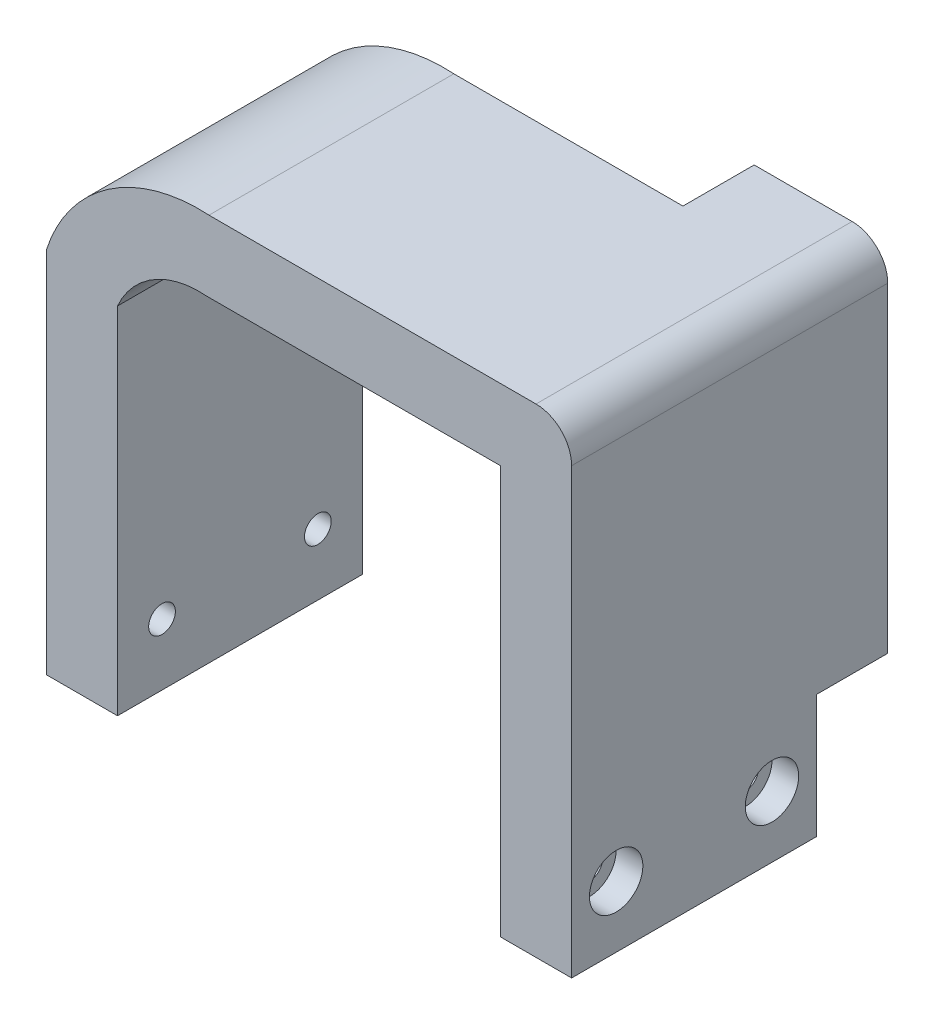
SolidWorks part; units mm, degrees
ref_plane "Front Plane" through (0, 0, 0) normal (0, 0, 1) x (1, 0, 0)
ref_plane "Top Plane" through (0, 0, 0) normal (0, 1, 0) x (1, 0, 0)
ref_plane "Right Plane" through (0, 0, 0) normal (1, 0, 0) x (0, 0, -1)
sketch "Sketch1" plane through (0, 0, 0) normal (0, 0, 1) x (1, 0, 0)
  line L0 (-27.2636, -0.8263) -> (-27.2636, 39.0321)
  line L1 (-17.2741, 45) -> (15.7364, 45)
  line L2 (15.7364, 45) -> (15.7364, -0.8263)
  line L8 (-35.2636, -0.8263) -> (-35.2636, 40.4496)
  line L9 (-16.9924, 53) -> (23.7364, 53)
  line L10 (23.7364, 53) -> (23.7364, -0.8263)
  line L11 (-27.2636, -0.8263) -> (-35.2636, -0.8263)
  line L12 (15.7364, -0.8263) -> (23.7364, -0.8263)
  line L13 (15.7364, 18) -> (15.7364, 40) construction
  arc A0 (-27.2636, 39.0321) -> (-17.2741, 45) centre (-18.0976, 35.034) cw
  arc A2 (-35.2636, 40.4496) -> (-16.9924, 53) centre (-18.0976, 35.034) cw
  dimension "D2" = 10
  dimension "D1" = 8
extrude "Boss-Extrude1" add sketch "Sketch1" along normal blind 27.5
sketch "Sketch3" plane through (0, 0, 0) normal (0, 0, -1) x (-1, 0, 0)
  line L0 (-15.7364, 13) -> (17.2741, 13) construction
  line L1 (-23.7364, 53) -> (-8.7364, 53)
  line L2 (-23.7364, 53) -> (-23.7364, 13)
  line L3 (-23.7364, 13) -> (-8.7364, 13)
  line L4 (-8.7364, 53) -> (-8.7364, 13)
  dimension "D2" = 15
extrude "Boss-Extrude2" add sketch "Sketch3" along normal blind 8
sketch "Sketch4" plane through (0, 0, 0) normal (0, 0, 1) x (1, 0, 0)
  circle A0 centre (12.7364, 42.5) radius 1.25
  circle A1 centre (12.7364, 42.5) radius 2
  circle A2 centre (12.7364, 15.5) radius 1.25
  circle A3 centre (12.7364, 15.5) radius 2
  dimension "D1" = 2.5
  dimension "D2" = 4
extrude "Cut-Extrude1" cut sketch "Sketch4" against normal through all contours A0 | A2 region at (12.7364, 42.5, 0) region at (12.7364, 15.5, 0)
extrude "Cut-Extrude2" cut sketch "Sketch4<3>" along normal blind 2 from surface starting at face at (13.9864, 42.5, -8)
sketch "Sketch4<3>" plane through (0, 0, 0) normal (0, 0, 1) x (1, 0, 0) same geometry as "Sketch4"
sketch "Sketch5" plane through (23.7364, 0, 0) normal (1, 0, 0) x (0, 0, -1)
  line L0 (0, -0.8263) -> (0, 13) construction
  line L1 (-27.5, -0.8263) -> (-27.5, 53) construction
  circle A0 centre (-5, 6.0869) radius 1.5
  circle A1 centre (-22.5, 6.0869) radius 1.5
  circle A2 centre (-22.5, 6.0869) radius 3
  circle A3 centre (-5, 6.0869) radius 3
  point P6 (0, 6.0869)
  dimension "D1" = 3
  dimension "D4" = 6
  dimension "D2" = 5
  dimension "D3" = 5
extrude "Cut-Extrude3" cut sketch "Sketch5" against normal through all contours A1 | A0 region at (23.7364, 6.0869, 5) region at (23.7364, 6.0869, 22.5)
extrude "Cut-Extrude4" cut sketch "Sketch5<3>" against normal blind 3
sketch "Sketch5<3>" plane through (23.7364, 0, 0) normal (1, 0, 0) x (0, 0, -1) same geometry as "Sketch5"
ref_plane "Plane1" through (-5.7636, 0, 0) normal (1, 0, 0) x (0, 0, -1)
mirror "Mirror1" about plane through (-5.7636, 0, 0) normal (1, 0, 0) of "Cut-Extrude4"
fillet "Fillet1" radius 4 1 edges at (23.7364, 53, 9.75)
